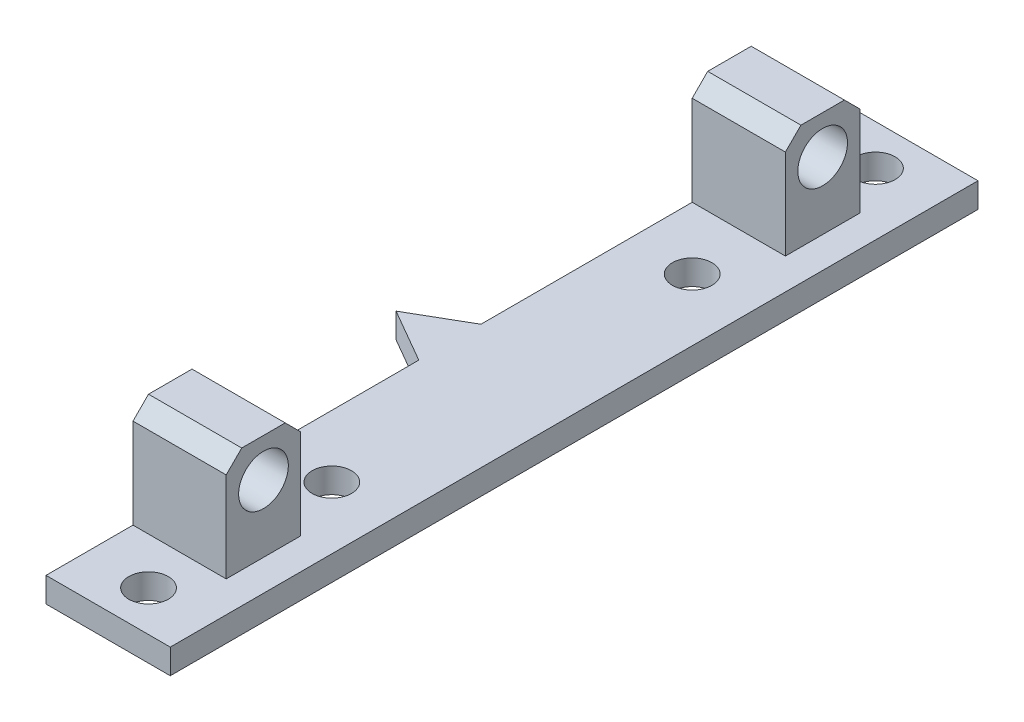
SolidWorks part; units mm, degrees
ref_plane "Front Plane" through (0, 0, 0) normal (0, 0, 1) x (1, 0, 0)
ref_plane "Top Plane" through (0, 0, 0) normal (0, 1, 0) x (1, 0, 0)
ref_plane "Right Plane" through (0, 0, 0) normal (1, 0, 0) x (0, 0, -1)
sketch "Sketch1" plane through (0, 0, 0) normal (0, 1, 0) x (1, 0, 0)
  line L1 (0, 0) -> (20, 0)
  line L2 (0, 0) -> (0, 130)
  line L3 (0, 130) -> (20, 130)
  line L4 (20, 0) -> (20, 130)
  dimension "D1" = 130
  dimension "D2" = 20
extrude "Boss-Extrude1" add sketch "Sketch1" along normal blind 4
sketch "Sketch2" plane through (0, 0, 0) normal (-1, 0, 0) x (0, 0, 1)
  line L0 (-130, 0) -> (0, 0) construction
  line L5 (-14, 18.5) -> (-16.5, 21)
  line L6 (-116, 0) -> (-104, 0)
  line L7 (-116, 0) -> (-116, 21)
  line L8 (-116, 21) -> (-104, 21)
  line L9 (-104, 0) -> (-104, 21)
  line L10 (-130, 0) -> (-116, 0) construction
  line L11 (-106.5, 21) -> (-104, 18.5)
  line L12 (-116, 18.5) -> (-113.5, 21)
  line L13 (-65, 0) -> (-65, 4) construction
  line L14 (-23.5, 21) -> (-26, 18.5)
  line L15 (-130, 4) -> (0, 4) construction
  line L16 (-26, 0) -> (-26, 21)
  line L17 (-14, 21) -> (-26, 21)
  line L18 (-14, 0) -> (-14, 21)
  line L19 (-14, 0) -> (-26, 0)
  circle A0 centre (-110, 14.8) radius 4
  circle A1 centre (-20, 14.8) radius 4
  point P10 (-110, 21)
  point P25 (-65, 4)
  point P30 (-20, 21)
  line M15 (0, 4) -> (-130, 4)
  dimension "D4" = 8
  dimension "D2" = 12
  dimension "D3" = 21
  dimension "D5" = 14.8
  dimension "D6" = 2.5
  dimension "D7" = 2.5
  dimension "D8" = 2.5
  dimension "D9" = 2.5
  dimension "D1" = 90
extrude "Boss-Extrude2" add sketch "Sketch2" against normal blind 15 contours L18 L5 L17 L14 L16 A1 M15 | L12 L7 L9 L11 L8 A0 M15 region at (0, 11.25, -14.2081) region at (0, 4.2081, -110)
sketch "Sketch3" plane through (0, 0, 0) normal (0, -1, 0) x (1, 0, 0)
  line L0 (0, -70) -> (-8.6603, -65)
  line L1 (0, -130) -> (0, 0) construction
  line L2 (-8.6603, -65) -> (0, -60)
  line L3 (0, -70) -> (0, -60)
  point P6 (0, -65)
  dimension "D1" = 10
  dimension "D2" = 10
  dimension "D3" = 10
extrude "Boss-Extrude3" add sketch "Sketch3" against normal up to surface (4 mm away) up to face at (8.3333, 4, -65)
sketch "Sketch4" plane through (0, 4, 0) normal (0, 1, 0) x (1, 0, 0)
  line L0 (10, 130) -> (10, 0) construction
  line L1 (20, 130) -> (0, 130) construction
  line L2 (0, 0) -> (20, 0) construction
  circle A0 centre (10, 123.5) radius 3.175
  circle A1 centre (10, 94) radius 3.175
  circle A2 centre (10, 36) radius 3.175
  circle A3 centre (10, 6.5) radius 3.175
  point P8 (0, 0)
  point P15 (10, 93.6421)
  point P16 (10, 123.3556)
  dimension "D1" = 6.35
  dimension "D2" = 6.5
  dimension "D3" = 36
  dimension "D4" = 6.5
  dimension "D5" = 36
extrude "Cut-Extrude1" cut sketch "Sketch4" against normal through all
equation "\"8mm hole\" = 8mm"
equation "\"D4@Sketch2\"= \"8mm hole\""
